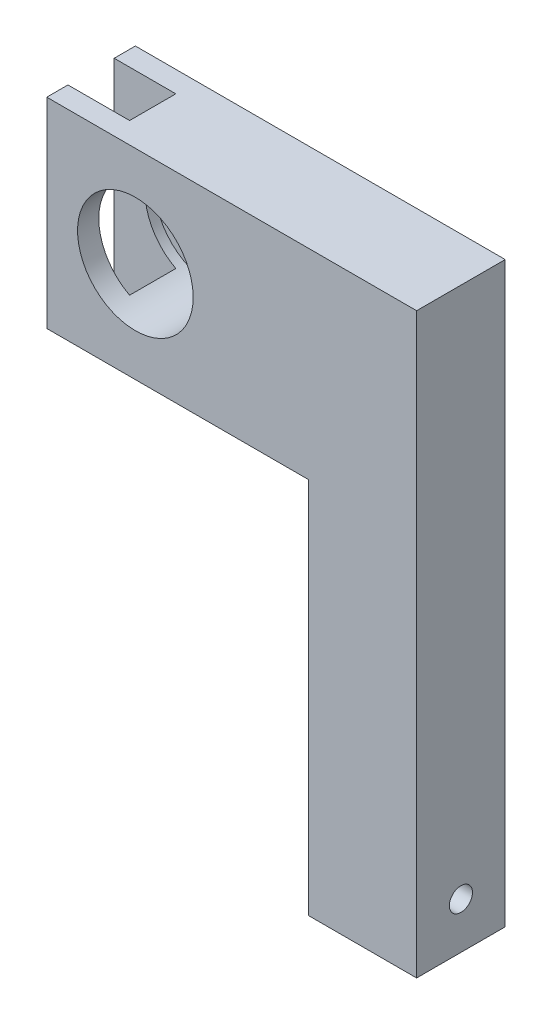
SolidWorks part; units mm, degrees
ref_plane "Front Plane" through (0, 0, 0) normal (0, 0, 1) x (1, 0, 0)
ref_plane "Top Plane" through (0, 0, 0) normal (0, 1, 0) x (1, 0, 0)
ref_plane "Right Plane" through (0, 0, 0) normal (1, 0, 0) x (0, 0, -1)
sketch "Sketch1" plane through (0, 0, 0) normal (0, 0, 1) x (1, 0, 0)
  line L0 (68, 98) -> (68, 0)
  line L1 (68, 0) -> (96, 0)
  line L2 (96, 0) -> (96, 150)
  line L3 (96, 150) -> (0, 150)
  line L4 (0, 150) -> (0, 98)
  line L5 (0, 98) -> (68, 98)
  circle A1 centre (23, 124) radius 15
  circle A2 centre (23, 124) radius 6
  point P9 (0, 0)
  point P11 (0, 124)
  point P12 (0, 0)
  dimension "D1" = 28
  dimension "D6" = 30
  dimension "D7" = 12
  dimension "D2" = 150
  dimension "D3" = 96
  dimension "D4" = 52
  dimension "D5" = 23
extrude "Boss-Extrude1" add sketch "Sketch1" along normal blind 23 contours L4 L5 L0 L1 L2 L3 A1 region at (34, 99.7809, 0)
extrude "Boss-Extrude2" add sketch "Sketch1<3>" along normal blind 3 contours A1 A2 region at (8.4243, 124, 0)
sketch "Sketch1<3>" plane through (0, 0, 0) normal (0, 0, 1) x (1, 0, 0) same geometry as "Sketch1"
sketch "Sketch2" plane through (0, 150, 0) normal (0, 1, 0) x (1, 0, 0)
  line L0 (0, -23) -> (0, 0) construction
  line L1 (0, -5.5) -> (16, -5.5)
  line L2 (0, -5.5) -> (0, -17.5)
  line L3 (0, -17.5) -> (16, -17.5)
  line L4 (16, -5.5) -> (16, -17.5)
  line L5 (96, 0) -> (0, 0) construction
  point P6 (16, -11.5)
  dimension "D1" = 12
  dimension "D2" = 16
  dimension "D3" = 11.5
extrude "Cut-Extrude1" cut sketch "Sketch2" against normal up to next
sketch "Sketch3" plane through (96, 0, 0) normal (1, 0, 0) x (0, 0, -1)
  line L0 (-23, 0) -> (-23, 150) construction
  line L1 (-23, 0) -> (0, 0) construction
  circle A0 centre (-11.5, 12) radius 3
  point P4 (0, 0)
  dimension "D1" = 6
  dimension "D2" = 11.5
  dimension "D3" = 12
extrude "Cut-Extrude2" cut sketch "Sketch3" against normal up to next
